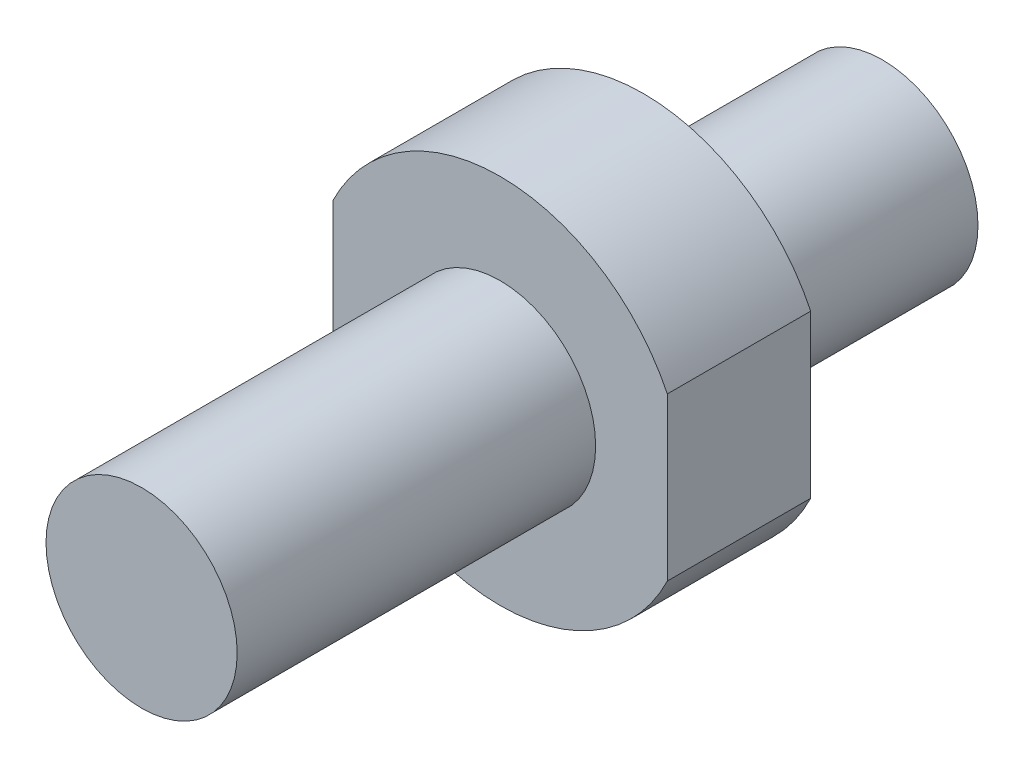
SolidWorks part; units mm, degrees
material "普通碳钢"
ref_plane "前视基准面" through (0, 0, 0) normal (0, 0, 1) x (1, 0, 0)
ref_plane "上视基准面" through (0, 0, 0) normal (0, 1, 0) x (1, 0, 0)
ref_plane "右视基准面" through (0, 0, 0) normal (1, 0, 0) x (0, 0, -1)
sketch "草图2" plane through (0, 0, 0) normal (1, 0, 0) x (0, 0, -1)
  line L0 (0, 0) -> (128.8801, 0) construction
  line L1 (0, 0) -> (0, 4)
  line L2 (0, 4) -> (15, 4)
  line L7 (15, 4) -> (15, 9)
  line L8 (15, 9) -> (21, 9)
  line L9 (21, 9) -> (21, 4)
  line L10 (21, 4) -> (31, 4)
  line L11 (31, 4) -> (31, 0)
  line L12 (0, 0) -> (31, 0)
  dimension "D1" = 15
  dimension "D2" = 4
  dimension "D6" = 6
  dimension "D7" = 4
  dimension "D8" = 9
  dimension "D9" = 10
revolve "旋转1" add sketch "草图2" angle 360 about L0
cosmetic thread "装饰螺纹线1" parameters "D1"=11, "D2"=7
sketch "草图3" plane through (0, 0, -15) normal (0, 0, 1) x (1, 0, 0)
  line L0 (0, 0) -> (0, -7.8258) construction
  line L1 (-7, 8.3859) -> (-15, 8.3859)
  line L2 (7, -8.438) -> (15, -8.438)
  line L3 (7, -8.438) -> (7, 8.3859)
  line L4 (7, 8.3859) -> (15, 8.3859)
  line L5 (15, -8.438) -> (15, 8.3859)
  line L6 (-7, -8.438) -> (-15, -8.438)
  line L7 (-7, -8.438) -> (-7, 8.3859)
  line L8 (-15, -8.438) -> (-15, 8.3859)
  dimension "D1" = 7
  dimension "D2" = 8
extrude "切除-拉伸1" cut sketch "草图3" against normal blind 10
hole_wizard "M4 螺纹孔1" positions "3D草图1" profile "草图4" tap size "M4" standard "Gb"
sketch3d "3D草图1"
  line L0 (0, 0, -31) -> (0, 0, -21) construction
  point P0 (0, 0, -31)
cosmetic thread "孔螺蚊线1" parameters "D1"=8, "D2"=4
sketch "草图4" plane through (0, 0, -31) normal (1, 0, 0) x (0, 1, 0)
  line L0 (0, 0) -> (0, 12.4914)
  line L1 (0, 12.4914) -> (1.65, 11.5)
  line L2 (1.65, 11.5) -> (1.65, 0)
  line L5 (1.65, 0) -> (0, 0)
  line L10 (0, 12.4914) -> (-1.65, 11.5) construction
  line L11 (0, -6.35) -> (0, 107.95) construction
  dimension "螺纹孔钻头直径" = 3.3
  dimension "螺纹孔钻头深度" = 11.5
  dimension "导头角度" = 118
sketch "草图5" plane through (0, 0, -21) normal (0, 0, -1) x (-1, 0, 0)
  circle A0 centre (0, 0) radius 7.7778
extrude "切除-拉伸2" cut sketch "草图5" against normal blind 10 flip side to cut
ref_axis "基准轴1" through (0, 0, -31) along (0, 0, 1)
